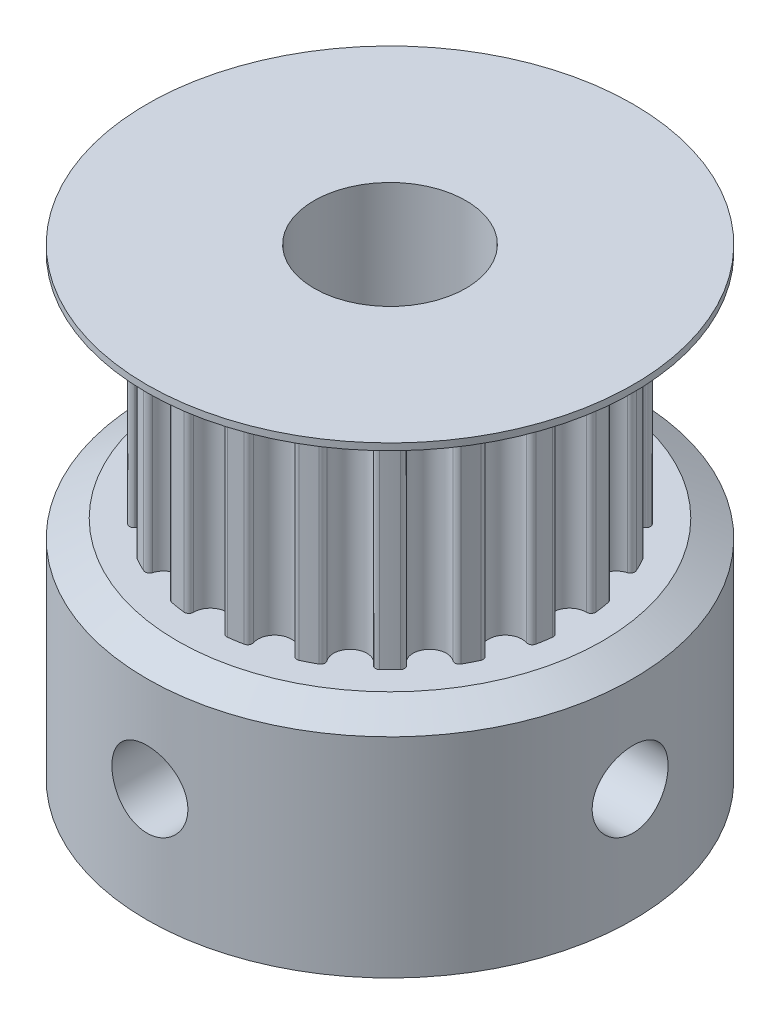
SolidWorks part; units mm, degrees
note: '?' marks a value the reader was unsure of.
material "1060 Alloy"
ref_plane "Спереди" through (0, 0, 0) normal (0, 0, 1) x (1, 0, 0)
ref_plane "Сверху" through (0, 0, 0) normal (0, 1, 0) x (1, 0, 0)
ref_plane "Справа" through (0, 0, 0) normal (1, 0, 0) x (0, 0, -1)
other "Configuration Table"
sketch "Эскиз1" plane through (0, 0, 0) normal (0, 1, 0) x (1, 0, 0)
  circle A0 centre (0, 0) radius 8
  circle A1 centre (0, 0) radius 2.5
  dimension "D1" = 16
  dimension "D2" = 5
extrude "Бобышка-Вытянуть1" add sketch "Эскиз1" along normal blind 7.45
sketch "Эскиз2" plane through (0, 7.45, 0) normal (0, 1, 0) x (1, 0, 0)
  arc A0 (-2.5575, 5.549) -> (-2.986, 5.3307) centre (0, 0) ccw
  circle A1 centre (0, 0) radius 2.5 construction
  circle A2 centre (0, 0) radius 2.5
  arc A3 (-0.55, 5.9169) -> (0.55, 5.9169) centre (0, 5.91) ccw
  arc A4 (1.3054, 5.7972) -> (2.3515, 5.4573) centre (1.8263, 5.6207) ccw
  arc A5 (3.0329, 5.1101) -> (3.9228, 4.4636) centre (3.4738, 4.7813) ccw
  arc A6 (4.4636, 3.9228) -> (5.1101, 3.0329) centre (4.7813, 3.4738) ccw
  arc A7 (5.4573, 2.3515) -> (5.7972, 1.3054) centre (5.6207, 1.8263) ccw
  arc A8 (5.9169, 0.55) -> (5.9169, -0.55) centre (5.91, 0) ccw
  arc A9 (5.7972, -1.3054) -> (5.4573, -2.3515) centre (5.6207, -1.8263) ccw
  arc A10 (5.1101, -3.0329) -> (4.4636, -3.9228) centre (4.7813, -3.4738) ccw
  arc A11 (3.9228, -4.4636) -> (3.0329, -5.1101) centre (3.4738, -4.7813) ccw
  arc A12 (2.3515, -5.4573) -> (1.3054, -5.7972) centre (1.8263, -5.6207) ccw
  arc A13 (0.55, -5.9169) -> (-0.55, -5.9169) centre (0, -5.91) ccw
  arc A14 (-1.3054, -5.7972) -> (-2.3515, -5.4573) centre (-1.8263, -5.6207) ccw
  arc A15 (-3.0329, -5.1101) -> (-3.9228, -4.4636) centre (-3.4738, -4.7813) ccw
  arc A16 (-4.4636, -3.9228) -> (-5.1101, -3.0329) centre (-4.7813, -3.4738) ccw
  arc A17 (-5.4573, -2.3515) -> (-5.7972, -1.3054) centre (-5.6207, -1.8263) ccw
  arc A18 (-5.9169, -0.55) -> (-5.9169, 0.55) centre (-5.91, 0) ccw
  arc A19 (-5.7972, 1.3054) -> (-5.4573, 2.3515) centre (-5.6207, 1.8263) ccw
  arc A20 (-5.1101, 3.0329) -> (-4.4636, 3.9228) centre (-4.7813, 3.4738) ccw
  arc A21 (-3.9228, 4.4636) -> (-3.0329, 5.1101) centre (-3.4738, 4.7813) ccw
  arc A22 (-2.3515, 5.4573) -> (-1.3054, 5.7972) centre (-1.8263, 5.6207) ccw
  arc A23 (-4.147, 4.4871) -> (-4.4871, 4.147) centre (0, 0) ccw
  arc A24 (-0.7176, 6.0677) -> (-1.1926, 5.9925) centre (0, 0) ccw
  arc A25 (1.1926, 5.9925) -> (0.7176, 6.0677) centre (0, 0) ccw
  arc A26 (2.986, 5.3307) -> (2.5575, 5.549) centre (0, 0) ccw
  arc A27 (4.4871, 4.147) -> (4.147, 4.4871) centre (0, 0) ccw
  arc A28 (5.549, 2.5575) -> (5.3307, 2.986) centre (0, 0) ccw
  arc A29 (6.0677, 0.7176) -> (5.9925, 1.1926) centre (0, 0) ccw
  arc A30 (-5.3307, 2.986) -> (-5.549, 2.5575) centre (0, 0) ccw
  arc A31 (-5.9925, 1.1926) -> (-6.0677, 0.7176) centre (0, 0) ccw
  arc A32 (-6.0677, -0.7176) -> (-5.9925, -1.1926) centre (0, 0) ccw
  arc A33 (-5.549, -2.5575) -> (-5.3307, -2.986) centre (0, 0) ccw
  arc A34 (-4.4871, -4.147) -> (-4.147, -4.4871) centre (0, 0) ccw
  arc A35 (-2.986, -5.3307) -> (-2.5575, -5.549) centre (0, 0) ccw
  arc A36 (5.9925, -1.1926) -> (6.0677, -0.7176) centre (0, 0) ccw
  arc A37 (5.3307, -2.986) -> (5.549, -2.5575) centre (0, 0) ccw
  arc A38 (4.147, -4.4871) -> (4.4871, -4.147) centre (0, 0) ccw
  arc A39 (2.5575, -5.549) -> (2.986, -5.3307) centre (0, 0) ccw
  arc A40 (0.7176, -6.0677) -> (1.1926, -5.9925) centre (0, 0) ccw
  arc A41 (-1.1926, -5.9925) -> (-0.7176, -6.0677) centre (0, 0) ccw
  arc A42 (5.9169, 0.55) -> (6.0677, 0.7176) centre (5.9188, 0.6999) ccw
  arc A43 (5.7972, 1.3054) -> (5.9925, 1.1926) centre (5.8454, 1.1633) cw
  arc A44 (5.4573, 2.3515) -> (5.549, 2.5575) centre (5.4128, 2.4947) ccw
  arc A45 (5.1101, 3.0329) -> (5.3307, 2.986) centre (5.1998, 2.9127) cw
  arc A46 (5.1101, -3.0329) -> (5.3307, -2.986) centre (5.1998, -2.9127) ccw
  arc A47 (5.4573, -2.3515) -> (5.549, -2.5575) centre (5.4128, -2.4947) cw
  arc A48 (5.7972, -1.3054) -> (5.9925, -1.1926) centre (5.8454, -1.1633) ccw
  arc A49 (5.9169, -0.55) -> (6.0677, -0.7176) centre (5.9188, -0.6999) cw
  arc A50 (3.9228, -4.4636) -> (4.147, -4.4871) centre (4.0452, -4.377) ccw
  arc A51 (4.4636, -3.9228) -> (4.4871, -4.147) centre (4.377, -4.0452) cw
  arc A52 (3.0329, -5.1101) -> (2.986, -5.3307) centre (2.9127, -5.1998) cw
  arc A53 (1.3054, -5.7972) -> (1.1926, -5.9925) centre (1.1633, -5.8454) cw
  arc A54 (0.55, -5.9169) -> (0.7176, -6.0677) centre (0.6999, -5.9188) ccw
  arc A55 (-0.55, -5.9169) -> (-0.7176, -6.0677) centre (-0.6999, -5.9188) cw
  arc A56 (-1.3054, -5.7972) -> (-1.1926, -5.9925) centre (-1.1633, -5.8454) ccw
  arc A57 (-2.3515, -5.4573) -> (-2.5575, -5.549) centre (-2.4947, -5.4128) cw
  arc A58 (-3.0329, -5.1101) -> (-2.986, -5.3307) centre (-2.9127, -5.1998) ccw
  arc A59 (-3.9228, -4.4636) -> (-4.147, -4.4871) centre (-4.0452, -4.377) cw
  arc A60 (-4.4636, -3.9228) -> (-4.4871, -4.147) centre (-4.377, -4.0452) ccw
  arc A61 (-5.9169, -0.55) -> (-6.0677, -0.7176) centre (-5.9188, -0.6999) ccw
  arc A62 (-5.7972, -1.3054) -> (-5.9925, -1.1926) centre (-5.8454, -1.1633) cw
  arc A63 (-5.4573, -2.3515) -> (-5.549, -2.5575) centre (-5.4128, -2.4947) ccw
  arc A64 (-5.1101, -3.0329) -> (-5.3307, -2.986) centre (-5.1998, -2.9127) cw
  arc A65 (-5.1101, 3.0329) -> (-5.3307, 2.986) centre (-5.1998, 2.9127) ccw
  arc A66 (-5.4573, 2.3515) -> (-5.549, 2.5575) centre (-5.4128, 2.4947) cw
  arc A67 (-5.7972, 1.3054) -> (-5.9925, 1.1926) centre (-5.8454, 1.1633) ccw
  arc A68 (-5.9169, 0.55) -> (-6.0677, 0.7176) centre (-5.9188, 0.6999) cw
  arc A69 (-4.4636, 3.9228) -> (-4.4871, 4.147) centre (-4.377, 4.0452) cw
  arc A70 (-3.9228, 4.4636) -> (-4.147, 4.4871) centre (-4.0452, 4.377) ccw
  arc A71 (-3.0329, 5.1101) -> (-2.986, 5.3307) centre (-2.9127, 5.1998) cw
  arc A72 (-2.3515, 5.4573) -> (-2.5575, 5.549) centre (-2.4947, 5.4128) ccw
  arc A73 (-1.3054, 5.7972) -> (-1.1926, 5.9925) centre (-1.1633, 5.8454) cw
  arc A74 (-0.55, 5.9169) -> (-0.7176, 6.0677) centre (-0.6999, 5.9188) ccw
  arc A75 (4.4636, 3.9228) -> (4.4871, 4.147) centre (4.377, 4.0452) ccw
  arc A76 (3.9228, 4.4636) -> (4.147, 4.4871) centre (4.0452, 4.377) cw
  arc A77 (0.55, 5.9169) -> (0.7176, 6.0677) centre (0.6999, 5.9188) cw
  arc A78 (1.3054, 5.7972) -> (1.1926, 5.9925) centre (1.1633, 5.8454) ccw
  arc A79 (3.0329, 5.1101) -> (2.986, 5.3307) centre (2.9127, 5.1998) ccw
  arc A80 (2.3515, 5.4573) -> (2.5575, 5.549) centre (2.4947, 5.4128) cw
  arc A81 (2.3515, -5.4573) -> (2.5575, -5.549) centre (2.4947, -5.4128) ccw
  point P69 (0, 0)
  point P135 (-0.5205, 6.0878)
  point P142 (0.5205, 6.0878)
  dimension "D1" = 12.22
  dimension "D2" = 1.1
  dimension "D3" = 0.75
  dimension "D5" = 0.15
  dimension "D6" = 0.15
  dimension "D4" = 20
extrude "Бобышка-Вытянуть2" add sketch "Эскиз2" along normal blind 7
sketch "Эскиз3" plane through (0, 14.45, 0) normal (0, 1, 0) x (1, 0, 0)
  circle A0 centre (0, 0) radius 2.5 construction
  circle A1 centre (0, 0) radius 2.5
  circle A2 centre (0, 0) radius 8 construction
  circle A3 centre (0, 0) radius 8
extrude "Бобышка-Вытянуть3" add sketch "Эскиз3" along normal blind 1.55
sketch "Эскиз4" plane through (0, 0, 0) normal (0, 0, 1) x (1, 0, 0)
  line L0 (-8, 3.725) -> (8, 3.725) construction
  line L1 (-8, 7.45) -> (-8, 0) construction
  line L2 (8, 0) -> (8, 7.45) construction
  circle A0 centre (0, 3.725) radius 1.25
  dimension "D1" = 2.5
extrude "Вырез-Вытянуть1" cut sketch "Эскиз4" along normal up to surface (7.9017 mm away)
sketch "Эскиз5" plane through (0, 0, 0) normal (1, 0, 0) x (0, 0, -1)
  line L0 (8, 3.725) -> (-7.9017, 3.725) construction
  line L1 (8, 0) -> (8, 7.45) construction
  circle A0 centre (0, 3.725) radius 1.25
  spline S1 degree 2 poles (-8, 4.975) (-7.8047, 3.725) (-8, 2.475) knots 0 0 0 1 1 1 weights 0.00675 0.008 0.00925 construction
  dimension "D1" = 2.5
extrude "Вырез-Вытянуть2" cut sketch "Эскиз5" along normal up to surface (7.9017 mm away)
sketch "Минимальный радиус ремня" plane through (0, 7.45, 0) normal (0, 1, 0) x (1, 0, 0)
  circle A0 centre (0, 0) radius 5.36
  arc A2 (-2.986, -5.3307) -> (-2.5575, -5.549) centre (0, 0) ccw construction
  dimension "D1" = 0.75
  dimension "D2" = 10.72
chamfer "Фаска1" distance 1 angle 30 2 edges at (0, 14.45, 8) (0, 7.45, 8)
ref_axis "Ось1" through (0, 16, 0) along (0, -1, 0)?
sketch "Sketch1" plane through (0, 16, 0) normal (0, 1, 0) x (1, 0, 0)
  circle A0 centre (0, 0) radius 8
  circle A1 centre (0, 0) radius 8 construction
extrude "Cut-Extrude1" cut sketch "Sketch1" against normal blind 0.75 and the other way through all
